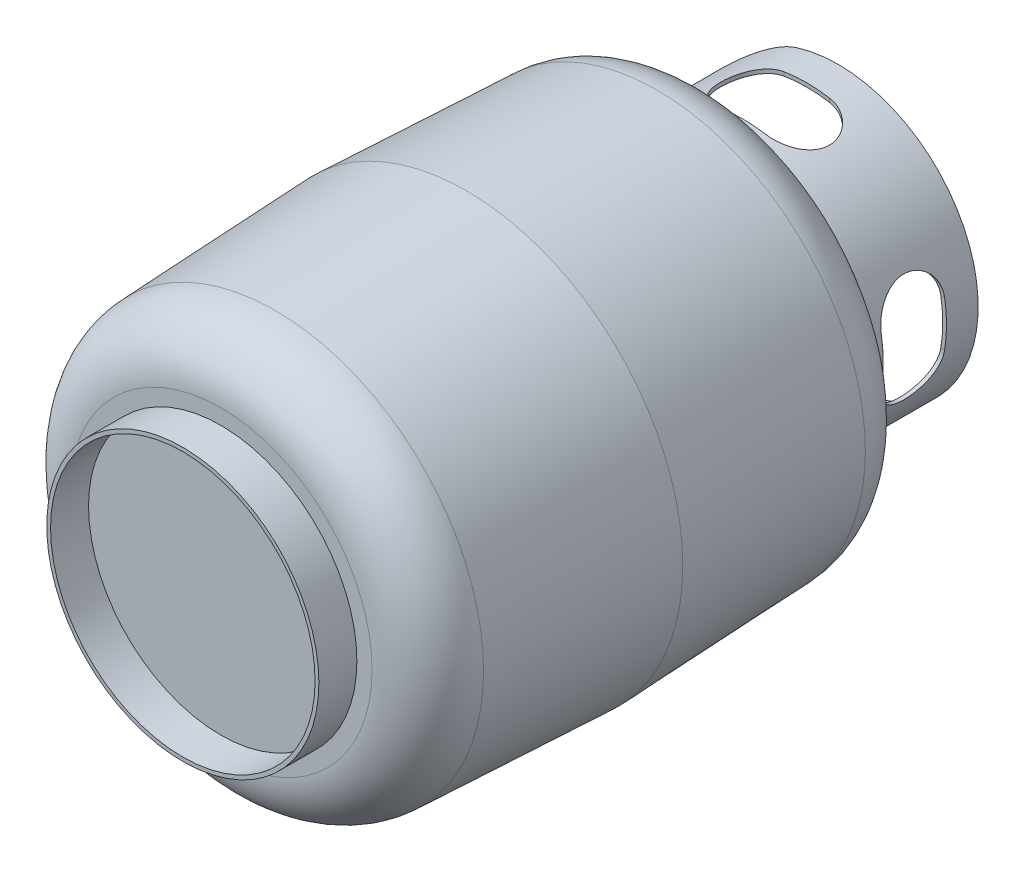
SolidWorks part; units mm, degrees
material "1060 Alloy"
ref_plane "Front Plane" through (0, 0, 0) normal (0, 0, 1) x (1, 0, 0)
ref_plane "Top Plane" through (0, 0, 0) normal (0, 1, 0) x (1, 0, 0)
ref_plane "Right Plane" through (0, 0, 0) normal (1, 0, 0) x (0, 0, -1)
sketch "Sketch1" plane through (0, 0, 0) normal (0, 1, 0) x (1, 0, 0)
  line L0 (0, -345.1104) -> (0, 638.9304) construction
  line L1 (0, 0) -> (119.4219, 0)
  line L2 (164.379, 43.0371) -> (170.9593, 193.75)
  line L3 (379.1696, 193.75) -> (-557.9263, 193.75) construction
  line L4 (164.379, 344.4629) -> (170.9593, 193.75)
  line L5 (119.4219, 387.5) -> (37, 387.5)
  line L6 (25, 399.5) -> (25, 407.5)
  line L7 (25, 407.5) -> (0, 407.5)
  line L8 (0, 0) -> (0, 407.5)
  arc A0 (37, 387.5) -> (25, 399.5) centre (37, 399.5) cw
  arc A1 (164.379, 344.4629) -> (119.4219, 387.5) centre (119.4219, 342.5) ccw
  arc A2 (119.4219, 0) -> (164.379, 43.0371) centre (119.4219, 45) ccw
  point P14 (25, 387.5)
  point P17 (162.5, 387.5)
  point P20 (162.5, 0)
  dimension "D4" = 50
  dimension "D6" = 12
  dimension "D7" = 45
  dimension "D8" = 45
  dimension "D1" = 325
  dimension "D2" = 387.5
  dimension "D3" = 92.5
  dimension "D5" = 20
revolve "Revolve2" add sketch "Sketch1" angle 360 about L8
shell "Shell1" thickness 4 removed face at (25, 0, -407.5)
sketch "Sketch2" plane through (0, 0, -387.5) normal (0, 0, -1) x (-1, 0, 0)
  line L0 (-107.4219, 0) -> (60, 0) construction
  line L1 (0, 107.4219) -> (0, -107.4219) construction
  line L2 (0, 0) -> (61.6147, 87.9948) construction
  line L3 (0, 0) -> (61.6147, -87.9948) construction
  line L4 (63.3354, 90.4523) -> (61.6147, 87.9948)
  line L5 (61.6147, -87.9948) -> (63.3354, -90.4523)
  arc A0 (61.6147, 87.9948) -> (61.6147, -87.9948) centre (0, 0) ccw
  circle A1 centre (0, 0) radius 119.4219 construction
  arc A2 (63.3354, 90.4523) -> (63.3354, -90.4523) centre (0, 0) ccw
  dimension "D1" = 12
  dimension "D4" = 3
  dimension "D2" = 55
  dimension "D3" = 55
extrude "Boss-Extrude1" add sketch "Sketch2" along normal blind 100
sketch "Sketch7" plane through (0, 0, 0) normal (1, 0, 0) x (0, 0, -1)
  line L0 (437.5, -18) -> (437.5, 18) construction
  line L1 (412.5, -18) -> (412.5, 18)
  line L2 (462.5, -18) -> (462.5, 18)
  line L3 (487.5, -107.4219) -> (487.5, 107.4219) construction
  line L5 (487.5, 0) -> (386.0628, 0) construction
  arc A0 (412.5, -18) -> (462.5, -18) centre (437.5, -18) ccw
  arc A1 (462.5, 18) -> (412.5, 18) centre (437.5, 18) ccw
  point P2 (437.5, 0)
  point P9 (487.5, 0)
  dimension "D1" = 50
  dimension "D3" = 25
  dimension "D2" = 36
extrude "Cut-Extrude3" cut sketch "Sketch7" along normal through all
sketch "Sketch10" plane through (0, 0, 0) normal (0, 1, 0) x (1, 0, 0)
  line L0 (-119.4219, 387.5) -> (119.4219, 387.5) construction
  line L1 (0, 387.5) -> (0, 487.5) construction
  line L2 (110.4219, 487.5) -> (-63.3354, 487.5) construction
  line L3 (-18, 437.5) -> (18, 437.5) construction
  line L4 (-18, 462.5) -> (18, 462.5)
  line L5 (-18, 412.5) -> (18, 412.5)
  arc A0 (-18, 462.5) -> (-18, 412.5) centre (-18, 437.5) ccw
  arc A1 (18, 412.5) -> (18, 462.5) centre (18, 437.5) ccw
  point P11 (0, 437.5)
  point P16 (-43, 437.5)
  point P17 (43, 437.5)
  dimension "D2" = 25
  dimension "D1" = 36
  dimension "D3" = 86
  dimension "D4" = 50
extrude "Cut-Extrude4" cut sketch "Sketch10" against normal through all and the other way through all
sketch "Sketch12" plane through (0, 0, 0) normal (0, 1, 0) x (1, 0, 0)
  line L0 (-63.3354, 487.5) -> (-63.3354, 387.5) construction
  line L1 (-63.3354, 487.5) -> (110.4219, 487.5) construction
  line L2 (-63.3354, 457.5) -> (-63.3354, 487.5)
  line L3 (-63.3354, 487.5) -> (-33.3354, 487.5)
  arc A0 (-33.3354, 487.5) -> (-63.3354, 457.5) centre (-33.3354, 457.5) ccw
  dimension "D1" = 60
extrude "Cut-Extrude5" cut sketch "Sketch12" against normal through all and the other way through all
sketch "Sketch13" plane through (0, 0, 0) normal (0, 0, 1) x (1, 0, 0)
  circle A0 centre (0, 0) radius 119.4219 construction
  circle A1 centre (0, 0) radius 107.4219
  circle A2 centre (0, 0) radius 104.4219
  dimension "D1" = 238.8437
  dimension "D2" = 12
  dimension "D3" = 3
extrude "Boss-Extrude2" add sketch "Sketch13" along normal blind 30
equation "\"A\"= 325mm"
equation "\"B\"= 387.5mm"
